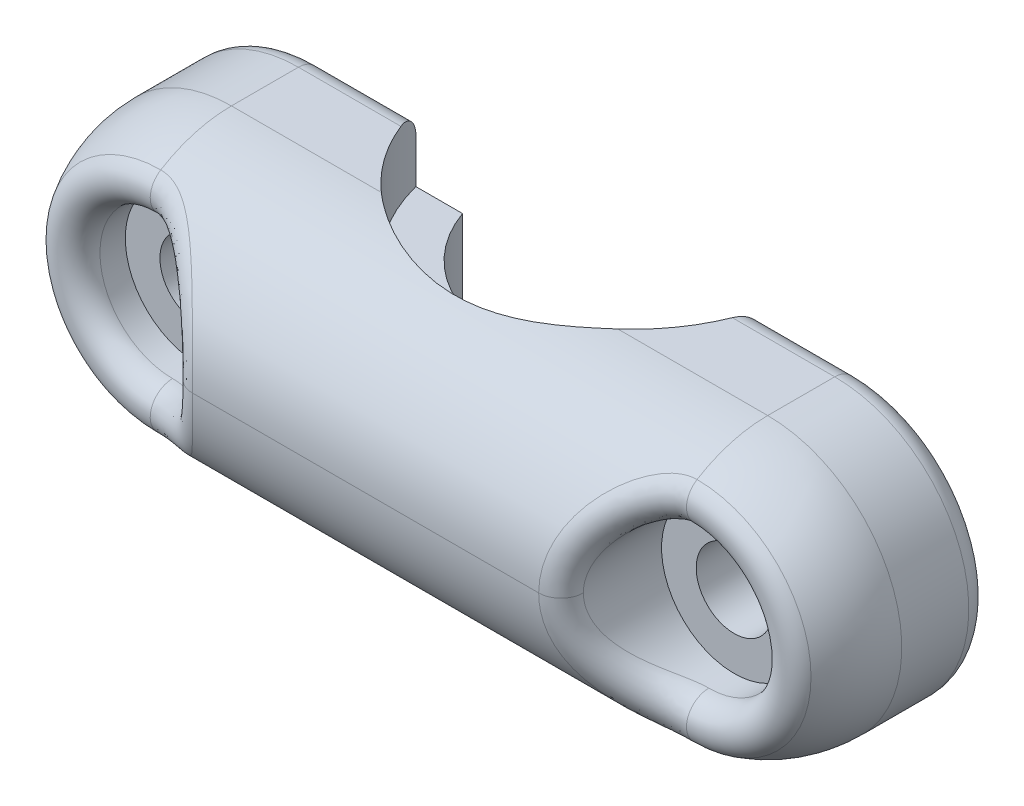
SolidWorks part; units mm, degrees
ref_plane "Front Plane" through (0, 0, 0) normal (0, 0, 1) x (1, 0, 0)
ref_plane "Top Plane" through (0, 0, 0) normal (0, 1, 0) x (1, 0, 0)
ref_plane "Right Plane" through (0, 0, 0) normal (1, 0, 0) x (0, 0, -1)
sketch "Sketch1" plane through (0, 0, 0) normal (0, 0, 1) x (1, 0, 0)
  line L0 (-12, 0) -> (12, 0) construction
  line L1 (-12, 6) -> (12, 6)
  line L2 (-12, -6) -> (12, -6)
  arc A0 (-12, 6) -> (-12, -6) centre (-12, 0) ccw
  arc A1 (12, -6) -> (12, 6) centre (12, 0) ccw
  point P2 (0, 0)
  dimension "D1" = 12
  dimension "D2" = 24
extrude "Boss-Extrude1" add sketch "Sketch1" along normal blind 10 from offset 2
hole_wizard "CBORE for M3 SHCS2" positions "Sketch11" profile "Sketch10" counterbore size "M3" standard "ANSI Metric" end condition through all
sketch "Sketch11" plane through (0, 0, 12) normal (0, 0, 1) x (1, 0, 0)
  arc A0 (-12, 6) -> (-12, -6) centre (-12, 0) ccw construction
  arc A1 (12, -6) -> (12, 6) centre (12, 0) ccw construction
  point P0 (-12, 0)
  point P2 (12, 0)
sketch "Sketch10" plane through (-12, 0, 12) normal (1, 0, 0) x (0, -1, 0)
  line L0 (0, 0) -> (0, 10)
  line L1 (0, 10) -> (1.7, 10)
  line L3 (1.7, 10) -> (1.7, 4.5)
  line L4 (1.7, 4.5) -> (3.25, 4.5)
  line L5 (3.25, 4.5) -> (3.25, 0)
  line L7 (3.25, 0) -> (0, 0)
  line L11 (0, -6.35) -> (0, 107.95) construction
  dimension "Thru Hole Dia." = 3.4
  dimension "Thru Hole Depth" = 10
  dimension "C'Bore Dia." = 6.5
  dimension "C'Bore Depth" = 4.5
fillet "Fillet2" radius 6 4 edges at (0, -6, 12) (0, 6, 12) (18, 0, 12) (-18, 0, 12)
fillet "Fillet1" radius 1 10 edges at (18, 0, 2) (0, -6, 2) (-18, 0, 2) (0, 6, 2) (9.3459, -1.8757, 11.6993) (10.1501, 2.6722, 11.3721) (-9.3459, 1.8757, 11.6993) (-10.1501, -2.6722, 11.3721) (-15.25, 0, 11.0436) (15.25, 0, 11.0436)
sketch "Sketch13" plane through (0, 0, 0) normal (1, 0, 0) x (0, 0, -1)
  line L0 (0, 6) -> (0, -6)
  line L1 (0, -6) -> (8, -6)
  line L2 (8, -6) -> (8, -3)
  line L3 (8, -3) -> (6, -3)
  line L4 (6, -3) -> (6, 3)
  line L5 (6, 3) -> (8, 3)
  line L6 (8, 3) -> (8, 6)
  line L7 (8, 6) -> (0, 6)
  line L8 (0, 6) -> (0, -6) construction
  dimension "D1" = 8
  dimension "D2" = 6
  dimension "D3" = 3
  dimension "D4" = 6
  dimension "D5" = 3
revolve "Cut-Revolve1" cut sketch "Sketch13" angle 360 about L0
